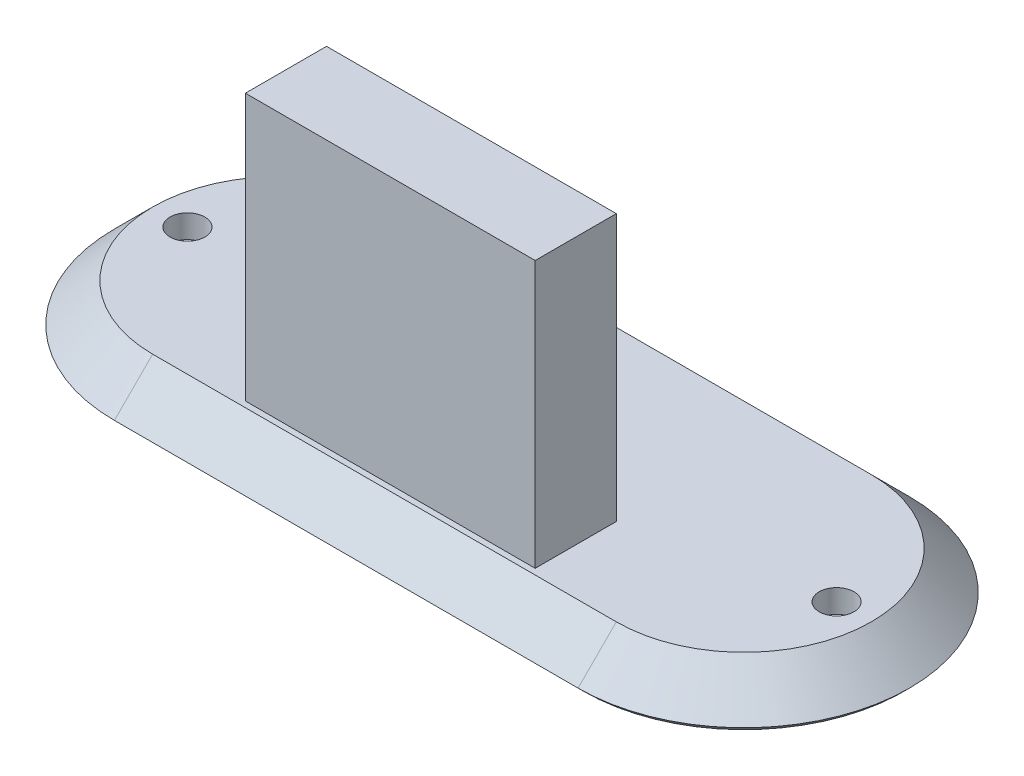
SolidWorks part; units mm, degrees
ref_plane "Plan de face" through (0, 0, 0) normal (0, 0, 1) x (1, 0, 0)
ref_plane "Plan de dessus" through (0, 0, 0) normal (0, 1, 0) x (1, 0, 0)
ref_plane "Plan de droite" through (0, 0, 0) normal (1, 0, 0) x (0, 0, -1)
sketch "Esquisse1" plane through (0, 0, 0) normal (0, 1, 0) x (1, 0, 0)
  line L0 (-20, 0) -> (20, 0) construction
  line L1 (-20, 14.8) -> (20, 14.8)
  line L2 (-20, -14.8) -> (20, -14.8)
  arc A0 (-20, 14.8) -> (-20, -14.8) centre (-20, 0) ccw
  arc A1 (20, -14.8) -> (20, 14.8) centre (20, 0) ccw
  point P3 (0, 0)
  dimension "D1" = 14.8
  dimension "D2" = 40
extrude "Boss.-Extru.1" add sketch "Esquisse1" along normal blind 3.8 draft 45
shell "Coque2" thickness 2 removed face at (0, 0, 0)
chamfer "Chanfrein1" distance 1 angle 45 4 edges at (-34.8, 0, 0) (0, 0, 14.8) (0, 0, -14.8) (34.8, 0, 0) first distance on face at (0, 0, 0)
sketch "Esquisse2" plane through (0, 3.8, 0) normal (0, 1, 0) x (1, 0, 0)
  line L0 (0, 11) -> (0, -11) construction
  line L1 (20, 11) -> (-20, 11) construction
  line L2 (-20, -11) -> (20, -11) construction
  circle A0 centre (-28, 0) radius 1.5
  circle A1 centre (28, 0) radius 1.5
  point P2 (0, 0)
  dimension "D1" = 3
  dimension "D2" = 8
extrude "Enlèv. mat.-Extru.1" cut sketch "Esquisse2" against normal up to next
sketch "Esquisse3" plane through (0, 3.8, 0) normal (0, 1, 0) x (1, 0, 0)
  line L0 (0, 0) -> (0, -8.5) construction
  line L1 (-10.5, -8.5) -> (10.5, -8.5)
  line L2 (-10.5, -8.5) -> (-10.5, -3.5)
  line L3 (12.5, -3.5) -> (12.5, -10.5)
  line L4 (-10.5, -3.5) -> (-12.5, -3.5)
  line L5 (-12.5, -3.5) -> (-12.5, -10.5)
  line L6 (-12.5, -10.5) -> (12.5, -10.5)
  line L7 (10.5, -3.5) -> (12.5, -3.5)
  line L8 (10.5, -8.5) -> (10.5, -3.5)
  point P5 (0, -10.5)
  dimension "D1" = 21
  dimension "D2" = 5
  dimension "D3" = 2
  dimension "D4" = 2
  dimension "D5" = 8.5
extrude "Boss.-Extru.2" add sketch "Esquisse3" along normal blind 21
sketch "Esquisse5" plane through (0, 24.8, 0) normal (0, 1, 0) x (1, 0, 0)
  line L1 (-12.5, -10.5) -> (12.5, -10.5)
  line L2 (-12.5, -10.5) -> (-12.5, -3.5)
  line L3 (-12.5, -3.5) -> (12.5, -3.5)
  line L4 (12.5, -10.5) -> (12.5, -3.5)
extrude "Boss.-Extru.3" add sketch "Esquisse5" along normal blind 2
sketch "Esquisse6" plane through (0, 3.8, 0) normal (0, 1, 0) x (1, 0, 0)
  line L0 (10.5, -8.5) -> (-10.5, -8.5) construction
  line L1 (-8, -8.5) -> (8, -8.5)
  line L2 (-8, -8.5) -> (-8, -6.5)
  line L3 (-8, -6.5) -> (8, -6.5)
  line L4 (0, -8.5) -> (0, 0) construction
  line L5 (8, -8.5) -> (8, -6.5)
  point P9 (0, -6.5)
  dimension "D1" = 2
  dimension "D2" = 16
extrude "Enlèv. mat.-Extru.2" cut sketch "Esquisse6" against normal blind 2
